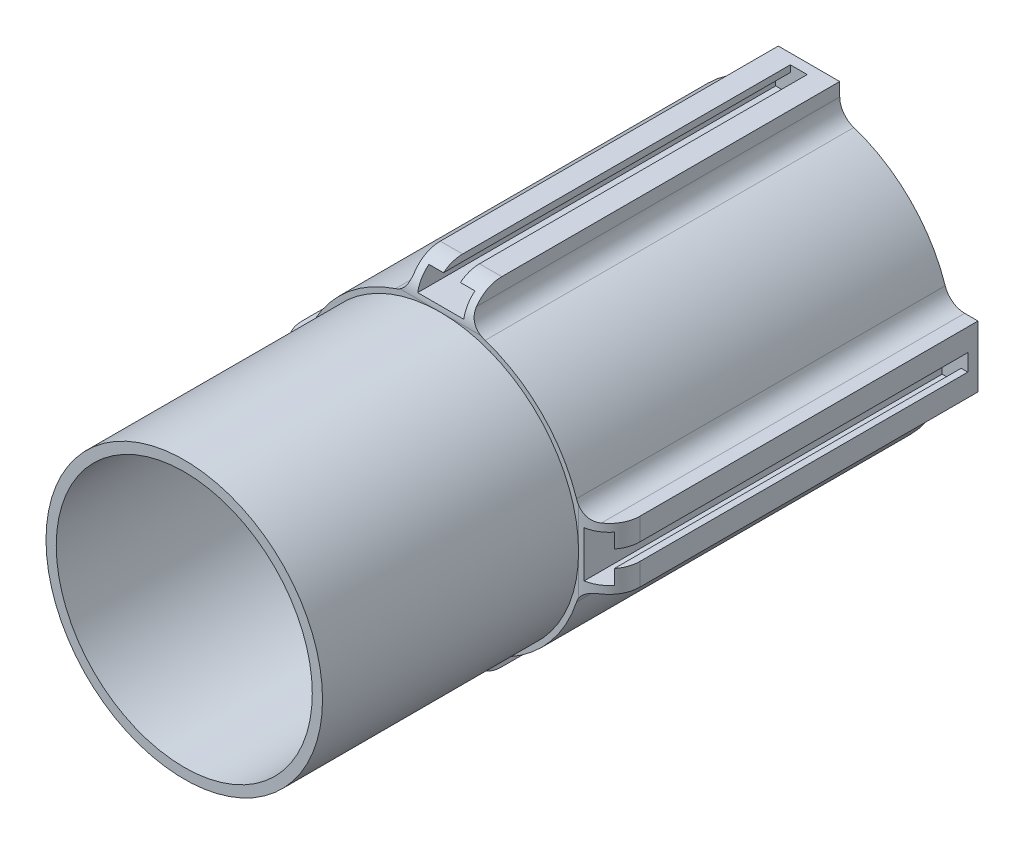
SolidWorks part; units mm, degrees
ref_plane "Alzado" through (0, 0, 0) normal (0, 0, 1) x (1, 0, 0)
ref_plane "Planta" through (0, 0, 0) normal (0, 1, 0) x (1, 0, 0)
ref_plane "Vista lateral" through (0, 0, 0) normal (1, 0, 0) x (0, 0, -1)
sketch "Croquis1" plane through (0, 0, 0) normal (0, 0, 1) x (1, 0, 0)
  circle A0 centre (0, 0) radius 14
  dimension "D1" = 28
extrude "Saliente-Extruir1" add sketch "Croquis1" against normal blind 36
sketch "Croquis2" plane through (0, 0, 0) normal (0, 0, 1) x (1, 0, 0)
  circle A0 centre (0, 0) radius 6.55
  dimension "D1" = 13.1
extrude "Cortar-Extruir1" cut sketch "Croquis2" against normal blind 33
sketch "Croquis3" plane through (0, 0, -33) normal (0, 0, 1) x (1, 0, 0)
  circle A0 centre (0, 0) radius 4.5
  dimension "D1" = 9
extrude "Cortar-Extruir2" cut sketch "Croquis3" against normal blind 1
shell "Vaciado3" thickness 1 removed face at (14, 0, -36) removed face at (14, 0, -36) removed face at (6.55, 0, 0)
sketch "Croquis4" plane through (0, 0, 0) normal (0, 0, 1) x (1, 0, 0)
  circle A0 centre (0, 0) radius 14
  dimension "D1" = 28
extrude "Extruir-Lámina1" add sketch "Croquis4" against normal blind 36 separate body thin thin type one direction reverse wall 1
sketch "Croquis11" plane through (0, 0, -34) normal (0, 0, 1) x (1, 0, 0)
  circle A0 centre (0, 0) radius 13
  dimension "D1" = 26
extrude "Saliente-Extruir2" add sketch "Croquis11" against normal blind 2
sketch "Croquis20" plane through (0, 0, -34) normal (0, 0, 1) x (1, 0, 0)
  circle A1 centre (0, 0) radius 4.5
  circle A2 centre (0, 0) radius 4.5
  dimension "D1" = 0
extrude "Cortar-Extruir8" cut sketch "Croquis20" against normal up to surface (2 mm away) up to face at (14, 0, -36)
ref_plane "Plano1" through (0, 14, 0) normal (0, 1, 0) x (1, 0, 0)
sketch "Croquis21" plane through (0, 14, 0) normal (0, 1, 0) x (1, 0, 0)
  line L0 (0, 0) -> (-3, 0)
  line L15 (-14, 0) -> (14, 0) construction
  line L16 (-3, 0) -> (-3, 36)
  line L17 (0, 0) -> (3, 0)
  line L18 (-3, 36) -> (3, 36)
  line L19 (3, 36) -> (3, 0)
  point P6 (0, 0)
  dimension "D1" = 3
  dimension "D2" = 36
  dimension "D3" = 3
extrude "Saliente-Extruir6" add sketch "Croquis21" against normal up to surface and the other way blind 2.5 up to face at (14, 0, -36)
sketch "Croquis29" plane through (0, 0, -36) normal (0, 0, -1) x (-1, 0, 0)
  line L0 (0, 0) -> (0, 14) construction
  line L1 (-2.25, 14) -> (2.25, 14)
  line L2 (-2.25, 14) -> (-2.25, 15.85)
  line L3 (-2.25, 15.85) -> (-0.825, 15.85)
  line L4 (-0.825, 15.85) -> (-0.825, 16.5)
  line L5 (-3, 16.5) -> (3, 16.5) construction
  line L6 (-0.825, 16.5) -> (0.825, 16.5)
  line L7 (0.825, 16.5) -> (0.825, 15.85)
  line L8 (0.825, 15.85) -> (2.25, 15.85)
  line L9 (2.25, 15.85) -> (2.25, 14)
  point P6 (0, 14)
  dimension "D1" = 14
  dimension "D2" = 4.5
  dimension "D3" = 1.85
  dimension "D4" = 1.425
  dimension "D5" = 1.65
  dimension "D6" = 0.65
  dimension "D7" = 1.425
extrude "Cortar-Extruir9" cut sketch "Croquis29" against normal blind 35
sketch "Croquis31" plane through (0, 0, 0) normal (0, 0, 1) x (1, 0, 0)
  circle A0 centre (0, 0) radius 13
extrude "Extruir-Lámina2" add sketch "Croquis31" against normal blind 0.5 thin thin type one direction reverse wall 6
sketch "Croquis33" plane through (0, 0, -36) normal (0, 0, -1) x (-1, 0, 0)
  circle A0 centre (0, 0) radius 13.5
  dimension "D1" = 27
extrude "Extruir-Lámina3" add sketch "Croquis33" along normal blind 25 thin thin type one direction reverse wall 1
fillet "Redondeo2" radius 2 2 edges at (-3, 13.6748, -18) (3, 13.6748, -18)
fillet "Redondeo6" radius 3 1 edges at (-1.9125, 16.5, -36)
ref_axis "Eje1" through (0, 0, -36) along (0, 0, 1)
pattern_circular "MatrizC1" count 4 over 360 about axis through (0, 0, -36) along (0, 0, 1) of "Saliente-Extruir6", "Cortar-Extruir9", "Redondeo2", "Redondeo6"
chamfer "Chaflán2" distance 2 angle 49 1 edges at (4.5, 0, -36) first distance on face at (4.5, 0, -36)
chamfer "Chaflán4" distance 6 angle 45 1 edges at (-12.5, 0, -36)
move or copy body "Sólido-Mover/Copiar2" bodies to move or copy 130 copy no rotation origin (0, 0, 0) rotation axis (0, 1, 0) rotation angle 180
sketch "Croquis34" plane through (0, 0, 0) normal (0, 1, 0) x (1, 0, 0)
  line L0 (-13, -34.0857) -> (-5.8809, -34.0857) construction
  line L7 (-5.8809, -34.0857) -> (-13, -42.0762) construction
  line L8 (-13, -42.0762) -> (-13, -34.0857) construction
  line L12 (-12.5, -40.7634) -> (-12.5, -34.5857)
  line L13 (-12.5, -34.5857) -> (-6.996, -34.5857)
  line L14 (-6.996, -34.5857) -> (-12.5, -40.7634)
  dimension "D1" = 0.5
revolve "Cortar-Revolución1" cut sketch "Croquis34" angle 360 about axis through (0, 0, -36) along (0, 0, 1)
sketch "Croquis35" plane through (0, 0, 34) normal (0, 0, -1) x (-1, 0, 0)
  line L0 (-13, 0) -> (-10.25, 0) construction
  circle A0 centre (0, 0) radius 13 construction
  circle A1 centre (-10.25, 0) radius 2.5
  dimension "D2" = 5
  dimension "D1" = 2.75
extrude "Cortar-Extruir11" cut sketch "Croquis35" against normal up to surface (0.5857 mm away) up to face at (-12.5, 0, 34.5857)
pattern_circular "MatrizC2" count 10 over 360 about axis through (0, 0, -36) along (0, 0, 1) of "Cortar-Extruir11"
sketch "Croquis38" plane through (0, 0, 0) normal (0, 0, -1) x (-1, 0, 0)
  circle A0 centre (0, 0) radius 6.5
  dimension "D1" = 13
extrude "Extruir-Lámina4" add sketch "Croquis38" against normal blind 15 thin thin type one direction wall 0.25
